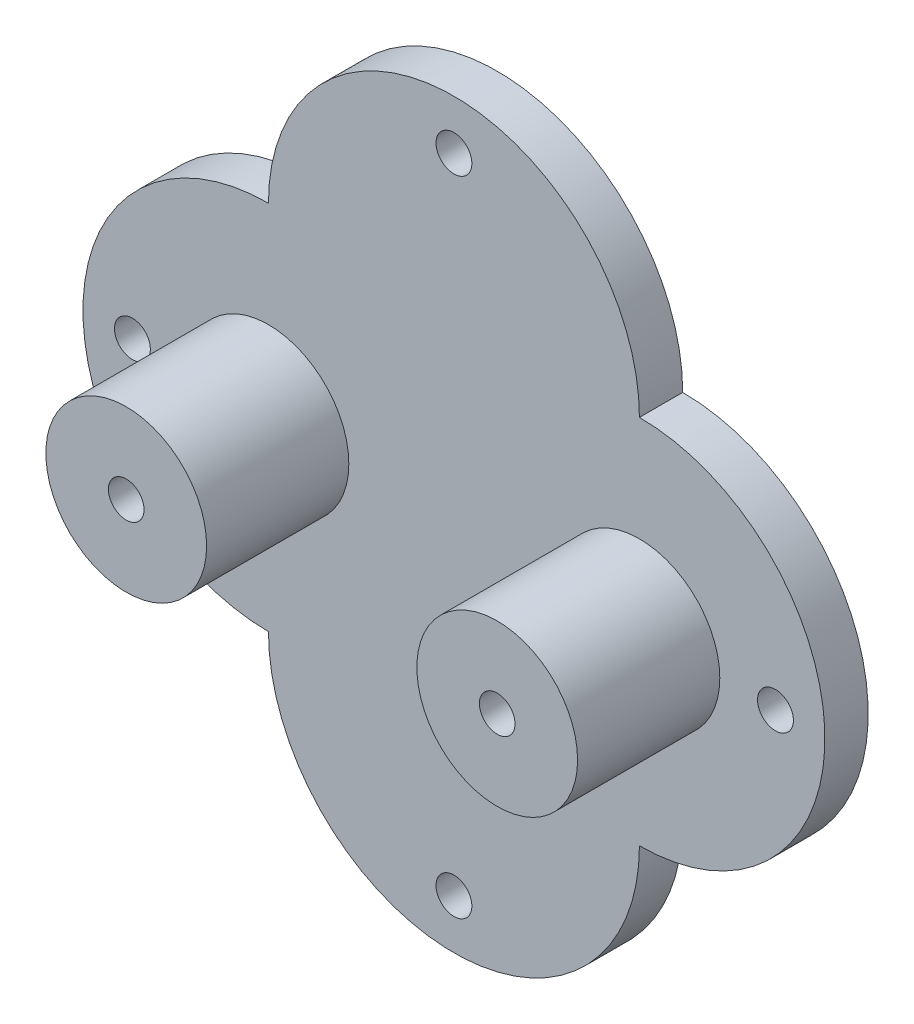
SolidWorks part; units mm, degrees
material "黄铜"
ref_plane "前视基准面" through (0, 0, 0) normal (0, 0, 1) x (1, 0, 0)
ref_plane "上视基准面" through (0, 0, 0) normal (0, 1, 0) x (1, 0, 0)
ref_plane "右视基准面" through (0, 0, 0) normal (1, 0, 0) x (0, 0, -1)
sketch "草图2" plane through (0, 0, 0) normal (0, 0, 1) x (1, 0, 0)
  line L0 (-15, 0) -> (15, 0) construction
  line L1 (-15, 15) -> (15, 15)
  line L2 (-15, -15) -> (15, -15)
  line L3 (0, -15) -> (0, 15) construction
  line L4 (-15, -15) -> (-15, 15)
  line L5 (15, -15) -> (15, 15)
  arc A0 (-15, 15) -> (-15, -15) centre (-15, 0) ccw
  arc A1 (15, -15) -> (15, 15) centre (15, 0) ccw
  arc A2 (-15, -15) -> (15, -15) centre (0, -15) ccw
  arc A3 (15, 15) -> (-15, 15) centre (0, 15) ccw
  point P2 (0, 0)
  point P9 (0, 0)
  dimension "D1" = 30
  dimension "D2" = 15
  dimension "D3" = 30
extrude "凸台-拉伸9" add sketch "草图2" along normal blind 2 contours L5 A1 | L1 A3 | L4 A0 | L2 A2 | L2 L5 L1 L4 region at (0, 21.3662, 0) region at (0, 0, 0) region at (-21.3662, 0, 0) region at (21.3662, 0, 0) region at (0, -21.3662, 0)
sketch "草图5" plane through (0, 0, 2) normal (0, 0, 1) x (1, 0, 0)
  circle A1 centre (-15, 0) radius 6.5
  circle A2 centre (15, 0) radius 6.5
  circle A3 centre (-15, 0) radius 1.44
  circle A4 centre (15, 0) radius 1.44
  dimension "D1" = 13
  dimension "D2" = 13
  dimension "D3" = 2.88
  dimension "D4" = 2.88
extrude "凸台-拉伸11" add sketch "草图5" along normal blind 9.7
extrude "凸台-拉伸12" add sketch "草图2<17>" along normal blind 3.5 contours L1 A3 | L2 L5 L1 L4 | L2 A2 | L5 A1 | L4 A0 region at (0, 21.3662, 0) region at (0, 0, 0) region at (-21.3662, 0, 0) region at (21.3662, 0, 0) region at (0, -21.3662, 0)
sketch "草图2<17>" plane through (0, 0, 0) normal (0, 0, 1) x (1, 0, 0) same geometry as "草图2"
extrude "凸台-拉伸13" add sketch "草图5<4>" along normal blind 10
sketch "草图5<4>" plane through (0, 0, 2) normal (0, 0, 1) x (1, 0, 0) same geometry as "草图5"
extrude "凸台-拉伸17" add sketch "草图5<8>" along normal blind 10 and the other way blind 2
sketch "草图5<8>" plane through (0, 0, 2) normal (0, 0, 1) x (1, 0, 0) same geometry as "草图5"
extrude "凸台-拉伸18" add sketch "草图5<11>" along normal blind 13
sketch "草图5<11>" plane through (0, 0, 2) normal (0, 0, 1) x (1, 0, 0) same geometry as "草图5"
extrude "凸台-拉伸19" add sketch "草图2<18>" along normal blind 3 contours L1 A3 | L2 L5 L1 L4 | L4 A0 | L5 A1 | L2 A2 region at (0, 21.3662, 0) region at (0, 0, 0) region at (-21.3662, 0, 0) region at (21.3662, 0, 0) region at (0, -21.3662, 0)
sketch "草图2<18>" plane through (0, 0, 0) normal (0, 0, 1) x (1, 0, 0) same geometry as "草图2"
sketch "草图6" plane through (0, 0, 3.5) normal (0, 0, 1) x (1, 0, 0)
  circle A0 centre (0, 26) radius 1.45
  circle A1 centre (-26, 0) radius 1.45
  circle A2 centre (26, 0) radius 1.45
  circle A3 centre (0, -26) radius 1.45
  dimension "D5" = 2.9
  dimension "D6" = 2.9
  dimension "D7" = 2.9
  dimension "D8" = 2.9
  dimension "D1" = 26
  dimension "D2" = 26
  dimension "D3" = 26
  dimension "D4" = 26
extrude "切除-拉伸1" cut sketch "草图6" against normal blind 3.5
